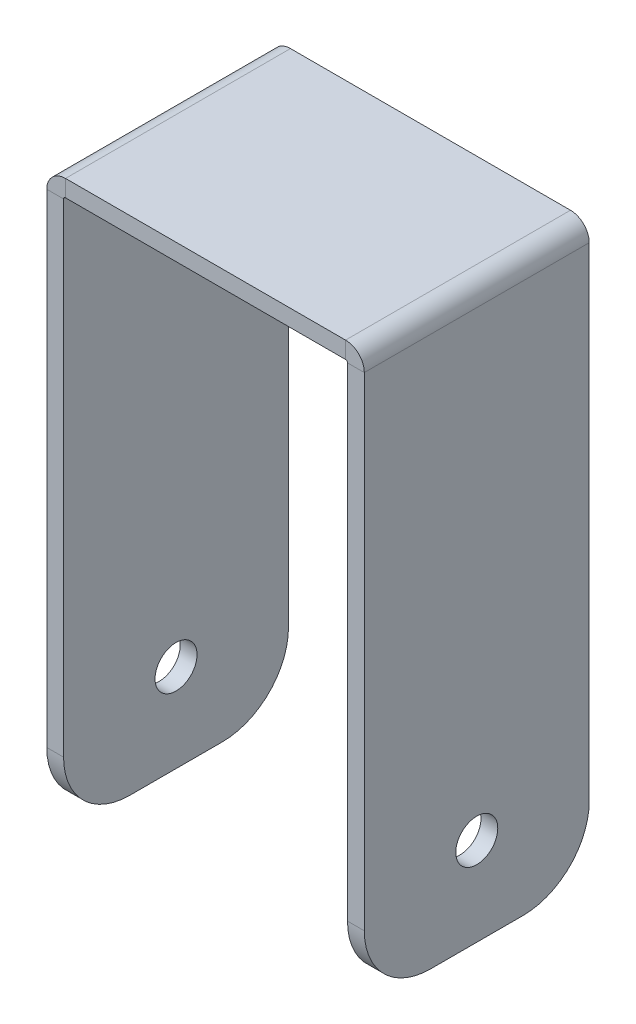
SolidWorks part; units mm, degrees
note: The reader was unsure of these and kept them because the rebuilt part matched: thickness of "Base-Flange1", "Edge-Flange1", "Sheet-Metal2", "Sheet-Metal3", "Sheet-Metal7"; flange length of "Edge-Flange1".
ref_plane "Front Plane" through (0, 0, 0) normal (0, 0, 1) x (1, 0, 0)
ref_plane "Top Plane" through (0, 0, 0) normal (0, 1, 0) x (1, 0, 0)
ref_plane "Right Plane" through (0, 0, 0) normal (1, 0, 0) x (0, 0, -1)
sketch "Sketch3" plane through (0, 0, 0) normal (0, 1, 0) x (1, 0, 0)
  line L1 (-60, 42.5) -> (60, 42.5)
  line L2 (-60, 42.5) -> (-60, -42.5)
  line L3 (-60, -42.5) -> (60, -42.5)
  line L4 (60, 42.5) -> (60, -42.5)
  line L5 (-60, 42.5) -> (60, -42.5) construction
  line L6 (-60, -42.5) -> (60, 42.5) construction
  point P0 (0, 0)
  dimension "D1" = 120
  dimension "D2" = 85
base flange "Base-Flange1" sketch "Sketch3" thickness 6.35 reverse thickness direction no parameters "D1"=0.7366
edge flange "Edge-Flange1" sketch "Sketch12" flange angle 90 flange length 214.7875 flange position material inside bend radius 0.7366 thickness 6.35 relief rectangular parameters "D6"=10
sketch "Sketch12" plane through (60, -6.35, 0) normal (-1, 0, 0) x (0, 0, -1)
  line L0 (42.5, 0) -> (-42.5, 0) construction
  line L2 (-42.5, 0) -> (-42.5, 208.4375)
  line L3 (-42.5, 208.4375) -> (42.5, 208.4375)
  line L4 (42.5, 208.4375) -> (42.5, 0)
  line L5 (42.5, 0) -> (-42.5, 0)
  line L6 (-42.5, 175.1) -> (42.5, 175.1) construction
  line L7 (0, 183.0375) -> (-42.5, 183.0375) construction
  circle A0 centre (0, 175.1) radius 7.9375
  dimension "D2" = 175.1
  dimension "D3" = 15.875
  dimension "D1" = 25.4
bend "EdgeBend1" bend radius 0.7366 bend angle 90 parameters "D5"=1
mirror "Mirror1" about plane through (0, 0, 0) normal (1, 0, 0) of "Edge-Flange1"
bend "MirrorBend1" bend radius 0.7366 bend angle 90 parameters "D5"=2
fillet "Fillet1" radius 25 4 edges at (-56.825, -214.7875, 42.5) (-56.825, -214.7875, -42.5) (56.825, -214.7875, -42.5) (56.825, -214.7875, 42.5)
sketch "Bend-Lines1" [suppressed] plane through (0, 0, 0) normal (0, 1, 0) x (1, 0, 0)
sketch "Bounding-Box1" [suppressed] plane through (0, 0, 0) normal (0, 1, 0) x (1, 0, 0)
sheet metal parameters "Sheet-Metal2" thickness 6.35 parameters "D1"=0.7366, "D7"=0.7366
flat pattern "Flat-Pattern2" [suppressed]
sketch "Bend-Lines2" plane through (0, 0, 0) normal (0, 1, 0) x (1, 0, 0)
sketch3d "Bounding-Box2" [suppressed]
  line L0 (-70, 35, 0) -> (70, 35, 0) construction
  line L1 (-70, -35, 0) -> (70, -35, 0) construction
  line L2 (-70, 35, 0) -> (-70, -35, 0) construction
  line L3 (70, 35, 0) -> (70, -35, 0) construction
sheet metal parameters "Sheet-Metal3" thickness 6.35 parameters "D1"=0.7366, "D7"=0.7366
flat pattern "Flat-Pattern2"
sketch "Bend-Lines2" plane through (0, 0, 0) normal (0, 1, 0) x (1, 0, 0)
  line L0 (40.9856, -42.5) -> (40.9856, 42.5) construction
  line L1 (40.9856, -42.5) -> (40.9856, 42.5) construction
sketch3d "Bounding-Box2" [suppressed]
  line L0 (243.3211, 42.5, 0) -> (-45, 42.5, 0) construction
  line L1 (243.3211, -42.5, 0) -> (-45, -42.5, 0) construction
  line L2 (243.3211, 42.5, 0) -> (243.3211, -42.5, 0) construction
  line L3 (-45, 42.5, 0) -> (-45, -42.5, 0) construction
bend of the flat pattern "Flatten-<EdgeBend1>1"
sheet metal parameters "Sheet-Metal7" thickness 6.35 parameters "D1"=0.7366, "D7"=0.7366
flat pattern "Flat-Pattern2"
sketch "Bend-Lines2" plane through (0, 0, 0) normal (0, 1, 0) x (1, 0, 0)
  line L0 (55.9856, -42.5) -> (55.9856, 42.5) construction
  line L1 (55.9856, -42.5) -> (55.9856, 42.5) construction
  line L2 (-55.9856, 42.5) -> (-55.9856, -42.5) construction
  line L3 (-55.9856, 42.5) -> (-55.9856, -42.5) construction
sketch3d "Bounding-Box2" [suppressed]
  line L0 (-266.7586, 42.5, 0) -> (266.7586, 42.5, 0) construction
  line L1 (-266.7586, -42.5, 0) -> (266.7586, -42.5, 0) construction
  line L2 (-266.7586, 42.5, 0) -> (-266.7586, -42.5, 0) construction
  line L3 (266.7586, 42.5, 0) -> (266.7586, -42.5, 0) construction
bend of the flat pattern "Flatten-<EdgeBend1>1"
bend of the flat pattern "Flatten-<MirrorBend1>1"
